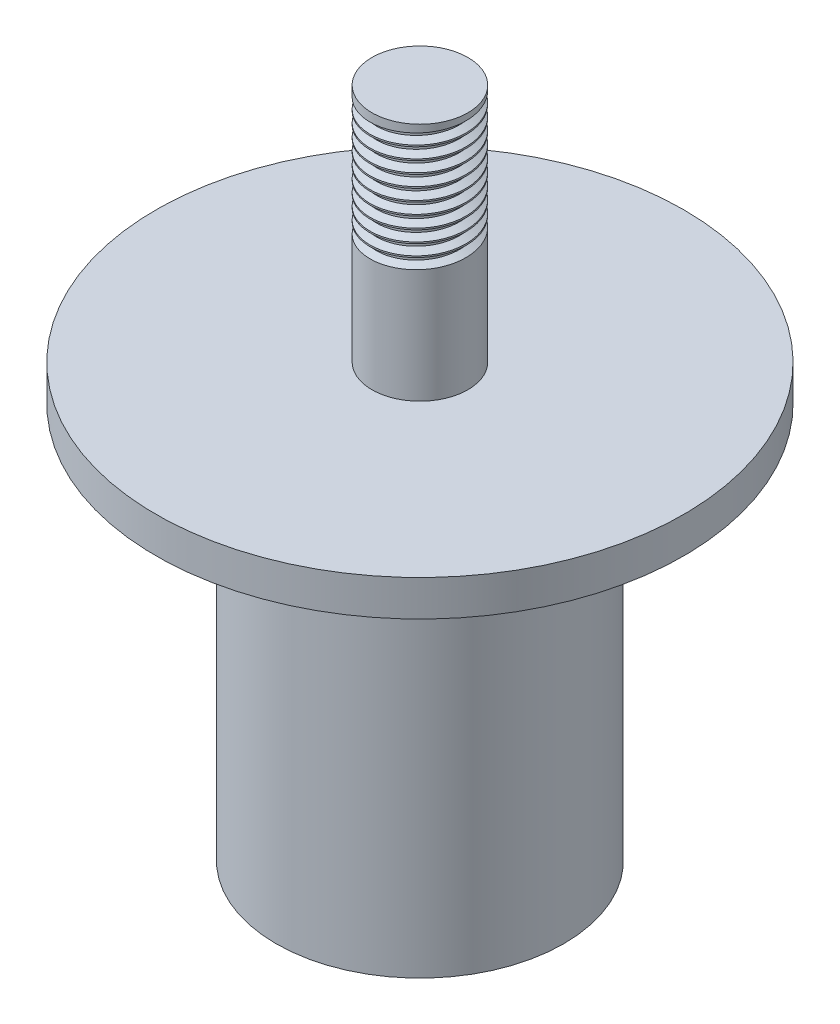
SolidWorks part; units mm, degrees
ref_plane "Front Plane" through (0, 0, 0) normal (0, 0, 1) x (1, 0, 0)
ref_plane "Top Plane" through (0, 0, 0) normal (0, 1, 0) x (1, 0, 0)
ref_plane "Right Plane" through (0, 0, 0) normal (1, 0, 0) x (0, 0, -1)
sketch "Sketch1" plane through (0, 0, 0) normal (0, 0, 1) x (1, 0, 0)
  line L0 (0, 0) -> (4, 0) construction
  line L2 (4, 0) -> (4, 3)
  line L3 (4, 3) -> (10, 3)
  line L4 (10, 3) -> (10, 33)
  line L5 (0, 0) -> (0, 58.7546) construction
  line L6 (10, 33) -> (0, 33)
  line L7 (0, 33) -> (0, 36)
  line L8 (4, 36) -> (22, 36)
  line L9 (22, 36) -> (22, 33)
  line L11 (12, 0) -> (12, 33)
  line L12 (12, 33) -> (22, 33)
  line L13 (4, 0) -> (12, 0)
  line L15 (4, 36) -> (4, 56)
  line L16 (4, 56) -> (0, 56)
  line L17 (0, 56) -> (0, 36)
  dimension "D1" = 10
  dimension "D2" = 4
  dimension "D3" = 2
  dimension "D4" = 22
  dimension "D5" = 3
  dimension "D6" = 3
  dimension "D7" = 30
revolve "Revolve1" add sketch "Sketch1" angle 360 about L5
thread "Thread1" pitch 1 method cut profile "Thread Profile1" start angle 0, offset 0, length 10, pitch 1, diameter 8
ref_plane "Plane1" through (-4, 56, 0) normal (0, 0, 1) x (-1, 0, 0)
sketch "Thread Profile1" plane through (-4, 56, 0) normal (0, 0, 1) x (-1, 0, 0)
  line L0 (0, 0) -> (0, 1) construction
  line L11 (0, 0) -> (0, 0.875)
  line L12 (0, 0.875) -> (-0.5413, 0.5625)
  line L13 (-0.5413, 0.5625) -> (-0.5413, 0.3125)
  line L15 (-0.5413, 0.3125) -> (0, 0)
  line L17 (-0.5413, 0.4375) -> (0, 0.4375) construction
  point P2 (0, 0)
  dimension "Pitch" = 1
  dimension "Profile_Angle" = 60
  dimension "Profile_Land" = 0.25
  dimension "Profile_Height" = 0.5413
